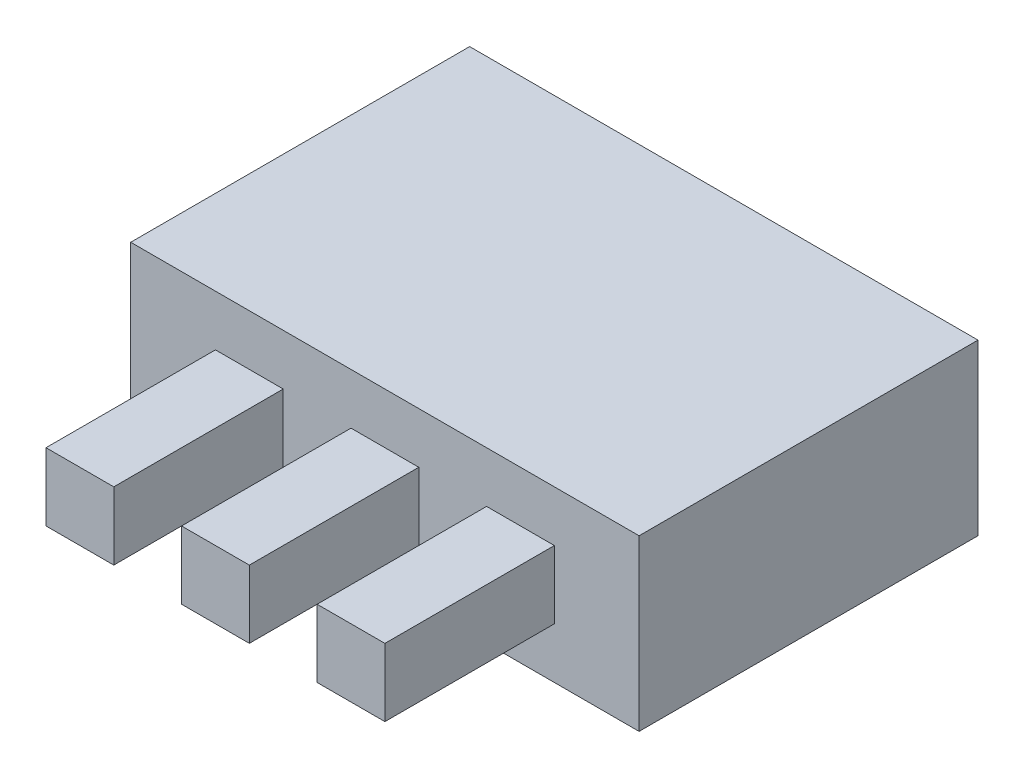
SolidWorks part; units mm, degrees
ref_plane "前视基准面" through (0, 0, 0) normal (0, 0, 1) x (1, 0, 0)
ref_plane "上视基准面" through (0, 0, 0) normal (0, 1, 0) x (1, 0, 0)
ref_plane "右视基准面" through (0, 0, 0) normal (1, 0, 0) x (0, 0, -1)
sketch "草图1" plane through (0, 0, 0) normal (0, 0, 1) x (1, 0, 0)
  line L0 (3, -1) -> (3, 1)
  line L1 (-7.5, -2.5) -> (7.5, -2.5)
  line L2 (-7.5, -2.5) -> (-7.5, 2.5)
  line L3 (-7.5, 2.5) -> (7.5, 2.5)
  line L4 (7.5, -2.5) -> (7.5, 2.5)
  line L5 (-7.5, -2.5) -> (7.5, 2.5) construction
  line L6 (-7.5, 2.5) -> (7.5, -2.5) construction
  line L7 (-1, -1) -> (1, -1)
  line L8 (-1, -1) -> (-1, 1)
  line L9 (-1, 1) -> (1, 1)
  line L10 (1, -1) -> (1, 1)
  line L11 (-1, -1) -> (1, 1) construction
  line L12 (-1, 1) -> (1, -1) construction
  line L13 (3, -1) -> (5, -1)
  line L14 (5, -1) -> (5, 1)
  line L15 (3, 1) -> (5, 1)
  line L16 (-5, -1) -> (-5, 1)
  line L17 (-5, -1) -> (-3, -1)
  line L18 (-3, -1) -> (-3, 1)
  line L19 (-5, 1) -> (-3, 1)
  point P0 (0, 0)
  point P6 (0, 0)
  dimension "D1" = 15
  dimension "D2" = 5
  dimension "D3" = 2
  dimension "D4" = 2
  dimension "D7" = 2
  dimension "D8" = 2
  dimension "D5" = 2
  dimension "D6" = 2
extrude "凸台-拉伸1" add sketch "草图1" along normal blind 10 contours L19 L16 L17 L18 | L7 L10 L9 L8 | L15 L0 L13 L14 | L1 L4 L3 L2 L10 L7 L8 L9 L0 L15 L14 L13 L16 L19 L18 L17 region at (4, 0, 0) region at (-7.3419, 0, 0) region at (0, 0, 0) region at (-4, 0, 0)
extrude "凸台-拉伸2" add sketch "草图1<3>" along normal blind 15 contours L19 L16 L17 L18 | L7 L10 L9 L8 | L15 L0 L13 L14 region at (4, 0, 0) region at (0, 0, 0) region at (-4, 0, 0)
sketch "草图1<3>" plane through (0, 0, 0) normal (0, 0, 1) x (1, 0, 0) same geometry as "草图1"
